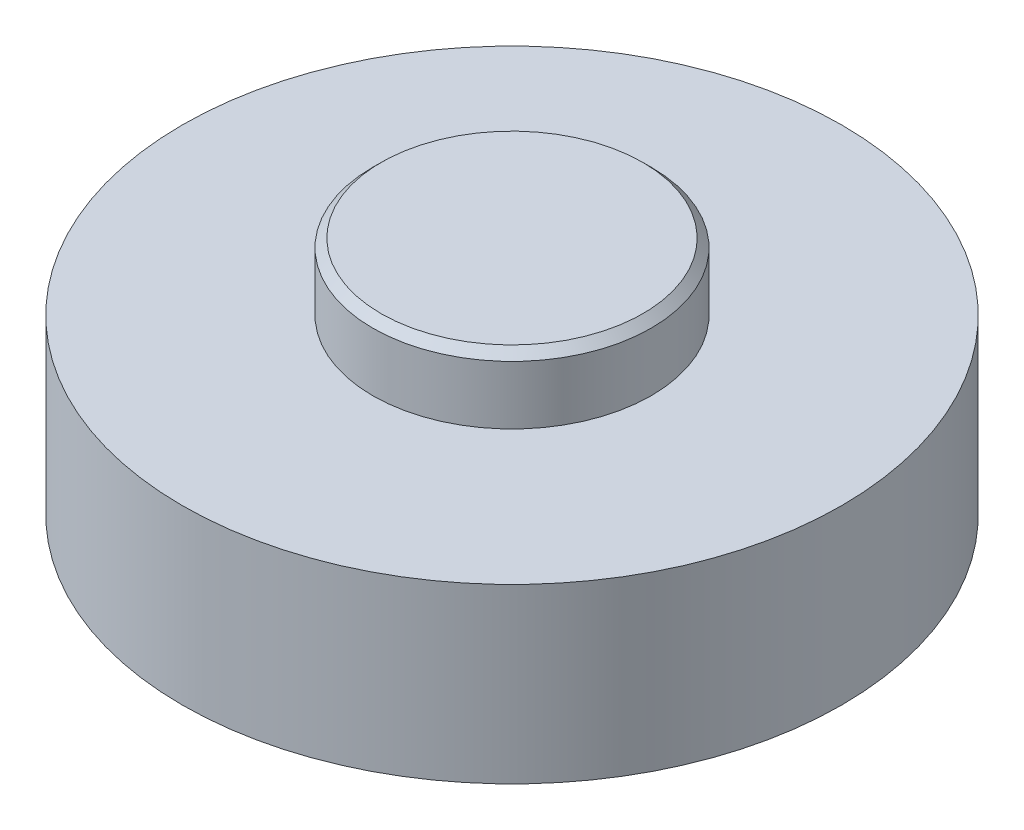
SolidWorks part; units mm, degrees
ref_plane "Front Plane" through (0, 0, 0) normal (0, 0, 1) x (1, 0, 0)
ref_plane "Top Plane" through (0, 0, 0) normal (0, 1, 0) x (1, 0, 0)
ref_plane "Right Plane" through (0, 0, 0) normal (1, 0, 0) x (0, 0, -1)
sketch "Sketch1" plane through (0, 0, 0) normal (0, 1, 0) x (1, 0, 0)
  line L16 (0, 8.9843) -> (0, -8.9843) construction
  line L17 (-3.0607, 9.4649) -> (-3.0607, 10.9843)
  line L18 (-2.5, 11.545) -> (2.5, 11.545)
  line L19 (3.0607, 10.9843) -> (3.0607, 9.4649)
  line L20 (9.4649, 3.0607) -> (10.9843, 3.0607)
  line L21 (11.545, 2.5) -> (11.545, -2.5)
  line L22 (10.9843, -3.0607) -> (9.4649, -3.0607)
  line L23 (3.0607, -9.4649) -> (3.0607, -10.9843)
  line L24 (2.5, -11.545) -> (-2.5, -11.545)
  line L25 (-3.0607, -10.9843) -> (-3.0607, -9.4649)
  line L26 (-9.4649, -3.0607) -> (-10.9843, -3.0607)
  line L27 (-11.545, -2.5) -> (-11.545, 2.5)
  line L28 (-10.9843, 3.0607) -> (-9.4649, 3.0607)
  arc A16 (-3.0607, 9.4649) -> (-9.4649, 3.0607) centre (0, 0) ccw
  circle A17 centre (0, 0) radius 15.0275
  arc A18 (-3.0607, 10.9843) -> (-2.5, 11.545) centre (-2.5, 10.9843) cw
  arc A19 (2.5, 11.545) -> (3.0607, 10.9843) centre (2.5, 10.9843) cw
  arc A20 (11.545, -2.5) -> (10.9843, -3.0607) centre (10.9843, -2.5) cw
  arc A21 (10.9843, 3.0607) -> (11.545, 2.5) centre (10.9843, 2.5) cw
  arc A22 (-2.5, -11.545) -> (-3.0607, -10.9843) centre (-2.5, -10.9843) cw
  arc A23 (3.0607, -10.9843) -> (2.5, -11.545) centre (2.5, -10.9843) cw
  arc A24 (-11.545, 2.5) -> (-10.9843, 3.0607) centre (-10.9843, 2.5) cw
  arc A25 (-10.9843, -3.0607) -> (-11.545, -2.5) centre (-10.9843, -2.5) cw
  arc A26 (9.4649, 3.0607) -> (3.0607, 9.4649) centre (0, 0) ccw
  arc A27 (3.0607, -9.4649) -> (9.4649, -3.0607) centre (0, 0) ccw
  arc A28 (-9.4649, -3.0607) -> (-3.0607, -9.4649) centre (0, 0) ccw
  point P2 (0, 0)
  point P13 (8.3786, 7.7975)
  point P17 (0, 0)
  point P41 (0, 0)
  line B0 (-3, -9.4843) -> (-3, -10.9843)
  line B1 (-2.5, -11.4843) -> (2.5, -11.4843)
  line B2 (3, -10.9843) -> (3, -9.4843)
  line B3 (2.5, -8.9843) -> (-2.5, -8.9843)
  line B4 (9.4843, -3) -> (10.9843, -3)
  line B5 (11.4843, -2.5) -> (11.4843, 2.5)
  line B6 (10.9843, 3) -> (9.4843, 3)
  line B7 (8.9843, 2.5) -> (8.9843, -2.5)
  line B8 (3, 9.4843) -> (3, 10.9843)
  line B9 (2.5, 11.4843) -> (-2.5, 11.4843)
  line B10 (-3, 10.9843) -> (-3, 9.4843)
  line B11 (-2.5, 8.9843) -> (2.5, 8.9843)
  line B12 (-9.4843, 3) -> (-10.9843, 3)
  line B13 (-11.4843, 2.5) -> (-11.4843, -2.5)
  line B14 (-10.9843, -3) -> (-9.4843, -3)
  line B15 (-8.9843, -2.5) -> (-8.9843, 2.5)
  arc B16 (-3, -10.9843) -> (-2.5, -11.4843) centre (-2.5, -10.9843) ccw
  arc B17 (2.5, -11.4843) -> (3, -10.9843) centre (2.5, -10.9843) ccw
  arc B18 (3, -9.4843) -> (2.5, -8.9843) centre (2.5, -9.4843) ccw
  arc B19 (-2.5, -8.9843) -> (-3, -9.4843) centre (-2.5, -9.4843) ccw
  arc B20 (10.9843, -3) -> (11.4843, -2.5) centre (10.9843, -2.5) ccw
  arc B21 (11.4843, 2.5) -> (10.9843, 3) centre (10.9843, 2.5) ccw
  arc B22 (9.4843, 3) -> (8.9843, 2.5) centre (9.4843, 2.5) ccw
  arc B23 (8.9843, -2.5) -> (9.4843, -3) centre (9.4843, -2.5) ccw
  arc B24 (3, 10.9843) -> (2.5, 11.4843) centre (2.5, 10.9843) ccw
  arc B25 (-2.5, 11.4843) -> (-3, 10.9843) centre (-2.5, 10.9843) ccw
  arc B26 (-3, 9.4843) -> (-2.5, 8.9843) centre (-2.5, 9.4843) ccw
  arc B27 (2.5, 8.9843) -> (3, 9.4843) centre (2.5, 9.4843) ccw
  arc B28 (-10.9843, 3) -> (-11.4843, 2.5) centre (-10.9843, 2.5) ccw
  arc B29 (-11.4843, -2.5) -> (-10.9843, -3) centre (-10.9843, -2.5) ccw
  arc B30 (-9.4843, -3) -> (-8.9843, -2.5) centre (-9.4843, -2.5) ccw
  arc B31 (-8.9843, 2.5) -> (-9.4843, 3) centre (-9.4843, 2.5) ccw
  dimension "D1" = 5.08
  dimension "D2" = 6.1214
  dimension "D3" = 4
sketch_block_instance "Block1-1"
sketch_block "Block1"
extrude "Boss-Extrude1" add sketch "Sketch1" along normal blind 6.096 contours A17 A28 L26 A25 L27 A24 L28 A16 L17 A18 L18 A19 L19 A26 L20 A21 L21 A20 L22 A27 L23 A23 L24 A22 L25 region at (-14.6025, 0, 0)
sketch "Sketch2" plane through (0, 6.096, 0) normal (0, 1, 0) x (1, 0, 0)
  circle A0 centre (0, 0) radius 15.0275
extrude "Boss-Extrude2" add sketch "Sketch2" along normal blind 1.778
chamfer "Chamfer1" distance 0.381 angle 45 20 edges at (3.0607, 0, 10.2246) (-3.0607, 0, 10.2246) (2.8965, 0, 11.3808) (-2.8965, 0, 11.3808) (0, 0, 11.545) (-10.2246, 0, 3.0607) (-10.2246, 0, -3.0607) (-11.3808, 0, 2.8965) (-11.3808, 0, -2.8965) (-11.545, 0, 0) (-3.0607, 0, -10.2246) (3.0607, 0, -10.2246) (-2.8965, 0, -11.3808) (2.8965, 0, -11.3808) (0, 0, -11.545) (10.2246, 0, -3.0607) (10.2246, 0, 3.0607) (11.3808, 0, -2.8965) (11.3808, 0, 2.8965) (11.545, 0, 0)
ref_axis "Axis1" through (0, -0.4953, 0) along (0, 1, 0)
sketch "Sketch3" plane through (0, 7.874, 0) normal (0, 1, 0) x (1, 0, 0)
  circle A0 centre (0, 0) radius 6.35
  dimension "D1" = 12.7
extrude "Boss-Extrude3" add sketch "Sketch3" along normal blind 3.048
chamfer "Chamfer2" distance 0.381 angle 45 1 edges at (0, 10.922, 6.35)
